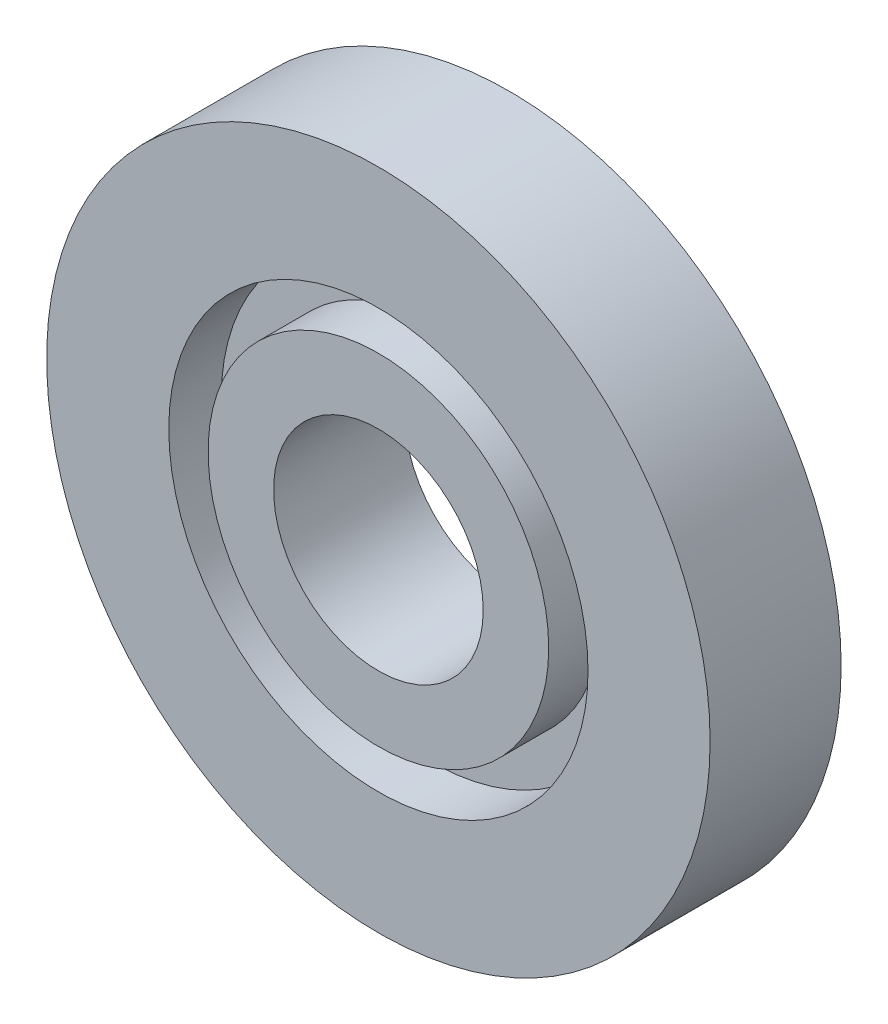
SolidWorks part; units mm, degrees
ref_plane "Alzado" through (0, 0, 0) normal (0, 0, 1) x (1, 0, 0)
ref_plane "Planta" through (0, 0, 0) normal (0, 1, 0) x (1, 0, 0)
ref_plane "Vista lateral" through (0, 0, 0) normal (1, 0, 0) x (0, 0, -1)
sketch "Croquis1" plane through (0, 0, 0) normal (0, 0, 1) x (1, 0, 0)
  circle A0 centre (0, 0) radius 6.33
  circle A1 centre (0, 0) radius 2.35
  dimension "D1" = 12.66
  dimension "D2" = 4.7
extrude "Saliente-Extruir2" add sketch "Croquis1" along normal blind 2.5 contours A0 A1 | A0 region at (-6.151, 0, 0)
sketch "Croquis2" plane through (0, 0, 2.5) normal (0, 0, 1) x (1, 0, 0)
  circle A0 centre (0, 0) radius 2
  dimension "D1" = 4
extrude "Cortar-Extruir1" cut sketch "Croquis2" against normal blind 5
sketch "Croquis3" plane through (0, 0, 2.5) normal (0, 0, 1) x (1, 0, 0)
  circle A0 centre (0, 0) radius 4
  circle A1 centre (0, 0) radius 3.25
  circle M3 centre (0, 0) radius 2
  dimension "D1" = 8
  dimension "D2" = 6.5
extrude "Cortar-Extruir2" cut sketch "Croquis3" against normal blind 1 contours A1 M3 | A0 region at (-3.1581, 0, 2.5)
sketch "Croquis4" plane through (0, 0, 0) normal (0, 0, -1) x (-1, 0, 0)
  circle A0 centre (0, 0) radius 4
  circle A1 centre (0, 0) radius 3.25
  dimension "D1" = 8
  dimension "D2" = 6.5
extrude "Cortar-Extruir3" cut sketch "Croquis4" against normal blind 1
